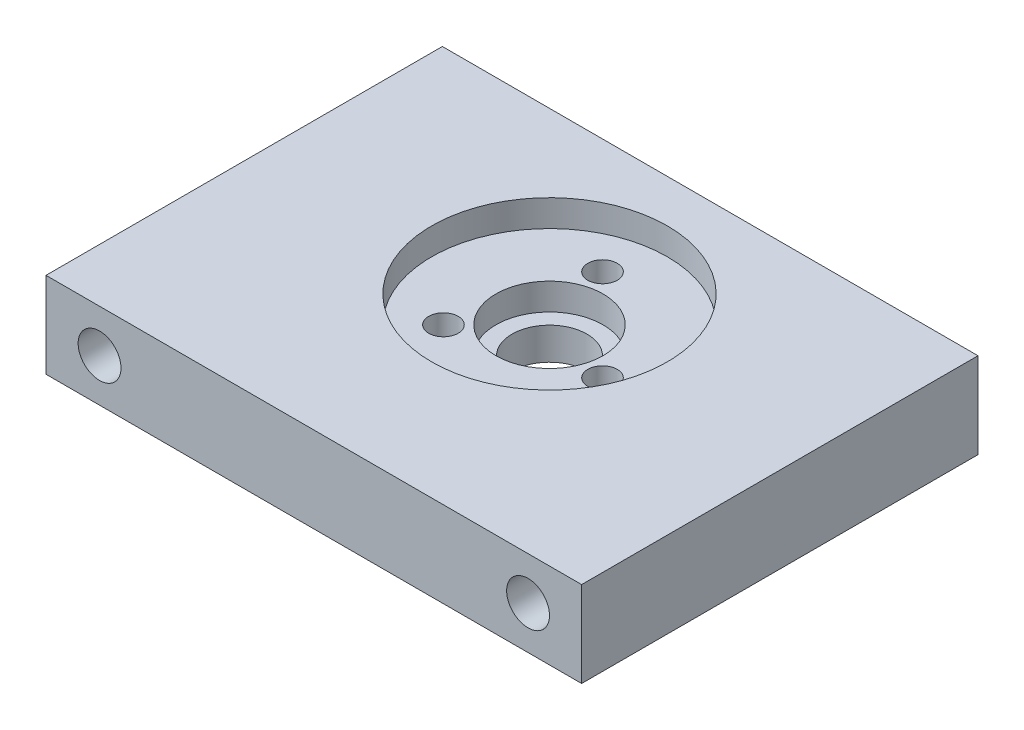
SolidWorks part; units mm, degrees
material "PVC rigide"
ref_plane "Plan de face" through (0, 0, 0) normal (0, 0, 1) x (1, 0, 0)
ref_plane "Plan de dessus" through (0, 0, 0) normal (0, 1, 0) x (1, 0, 0)
ref_plane "Plan de droite" through (0, 0, 0) normal (1, 0, 0) x (0, 0, -1)
sketch "Esquisse1" plane through (0, 0, 0) normal (0, 1, 0) x (1, 0, 0)
  line L1 (-25, 18.5) -> (25, 18.5)
  line L2 (-25, 18.5) -> (-25, -18.5)
  line L3 (-25, -18.5) -> (25, -18.5)
  line L4 (25, 18.5) -> (25, -18.5)
  line L5 (-25, -18.5) -> (25, 18.5) construction
  line L6 (25, -18.5) -> (-25, 18.5) construction
  point P4 (0, 0)
  dimension "D1" = 50
  dimension "D2" = 37
extrude "Boss.-Extru.1" add sketch "Esquisse1" along normal blind 8
sketch "Esquisse2" plane through (0, 8, 0) normal (0, 1, 0) x (1, 0, 0)
  line L1 (-25, 18.5) -> (25, 18.5) construction
  line L2 (0, 18.5) -> (0, -18.5) construction
  line L3 (25, 18.5) -> (-25, 18.5) construction
  line L4 (-25, -18.5) -> (25, -18.5) construction
  circle A0 centre (0, 3.5) radius 5
  dimension "D2" = 10
  dimension "D1" = 15
extrude "Enlèv. mat.-Extru.1" cut sketch "Esquisse2" against normal blind 5
sketch "Esquisse3" plane through (0, 8, 0) normal (0, 1, 0) x (1, 0, 0)
  line L0 (-4.9497, -1.4497) -> (-1.8117, 10.2615) construction
  line L1 (-1.8117, 10.2615) -> (6.7615, 1.6883) construction
  line L2 (6.7615, 1.6883) -> (-4.9497, -1.4497) construction
  line L3 (0, 3.5) -> (-1.8117, 10.2615) construction
  line L5 (0, -18.5) -> (0, 18.5) construction
  line L6 (-25, -18.5) -> (25, -18.5) construction
  line L7 (25, 18.5) -> (-25, 18.5) construction
  circle A0 centre (0, 3.5) radius 7 construction
  circle A1 centre (-1.8117, 10.2615) radius 1.375
  circle A2 centre (6.7615, 1.6883) radius 1.375
  circle A3 centre (-4.9497, -1.4497) radius 1.375
  circle A4 centre (0, 3.5) radius 3.5
  dimension "D1" = 14
  dimension "D2" = 2.75
  dimension "D3" = 7
  dimension "D4" = 15
extrude "Enlèv. mat.-Extru.2" cut sketch "Esquisse3" against normal blind 15
sketch "Esquisse4" plane through (0, 8, 0) normal (0, 1, 0) x (1, 0, 0)
  circle A0 centre (0, 3.5) radius 11
  dimension "D1" = 22
extrude "Enlèv. mat.-Extru.3" cut sketch "Esquisse4" against normal blind 2.5
sketch "Esquisse5" plane through (0, 0, 0) normal (0, -1, 0) x (1, 0, 0)
  circle A0 centre (-4.9497, 1.4497) radius 2.25
  circle A1 centre (6.7615, -1.6883) radius 2.25
  circle A2 centre (-1.8117, -10.2615) radius 2.25
  dimension "D1" = 4.5
extrude "Enlèv. mat.-Extru.4" cut sketch "Esquisse5" against normal blind 2.5
sketch "Esquisse6" plane through (0, 0, 18.5) normal (0, 0, 1) x (1, 0, 0)
  line L0 (-25, 4) -> (25, 4) construction
  line L1 (-25, 8) -> (-25, 0) construction
  line L2 (25, 8) -> (25, 0) construction
  circle A0 centre (-20, 4) radius 2
  circle A1 centre (20, 4) radius 2
  dimension "D1" = 4
  dimension "D2" = 5
  dimension "D3" = 5
extrude "Enlèv. mat.-Extru.5" cut sketch "Esquisse6" against normal blind 10
